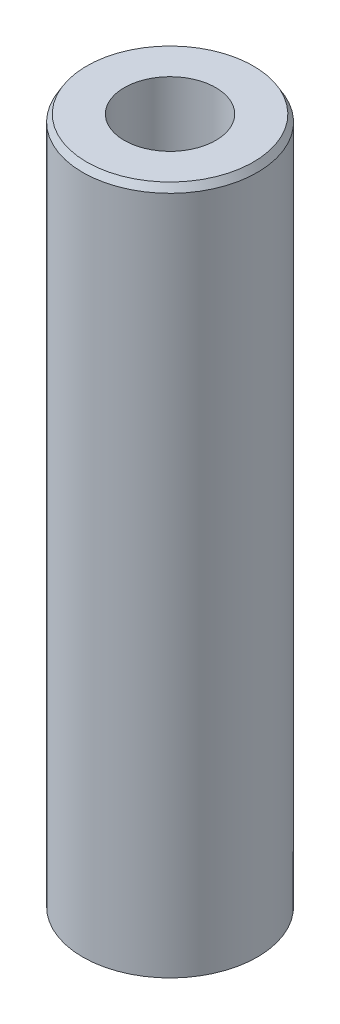
SolidWorks part; units mm, degrees
ref_plane "Front Plane" through (0, 0, 0) normal (0, 0, 1) x (1, 0, 0)
ref_plane "Top Plane" through (0, 0, 0) normal (0, 1, 0) x (1, 0, 0)
ref_plane "Right Plane" through (0, 0, 0) normal (1, 0, 0) x (0, 0, -1)
sketch "Sketch1" plane through (0, 0, 0) normal (0, 1, 0) x (1, 0, 0)
  circle A0 centre (0, 0) radius 32.5
  dimension "SHAFT_OD" = 65
extrude "Boss-Extrude1" add sketch "Sketch1" along normal blind 256.9827
sketch "Sketch2" plane through (0, 0, 0) normal (0, 1, 0) x (1, 0, 0)
  circle A0 centre (0, 0) radius 17.0316
  dimension "BORE_D" = 34.0631
extrude "Cut-Extrude1" cut sketch "Sketch2" along normal through all
chamfer "Chamfer1" distance 2.5899 angle 30 2 edges at (0, 256.9827, 32.5) (0, 0, 32.5) first distance on face at (0, 256.9827, 32.5) first distance on face at (0, 0, 17.0316)
